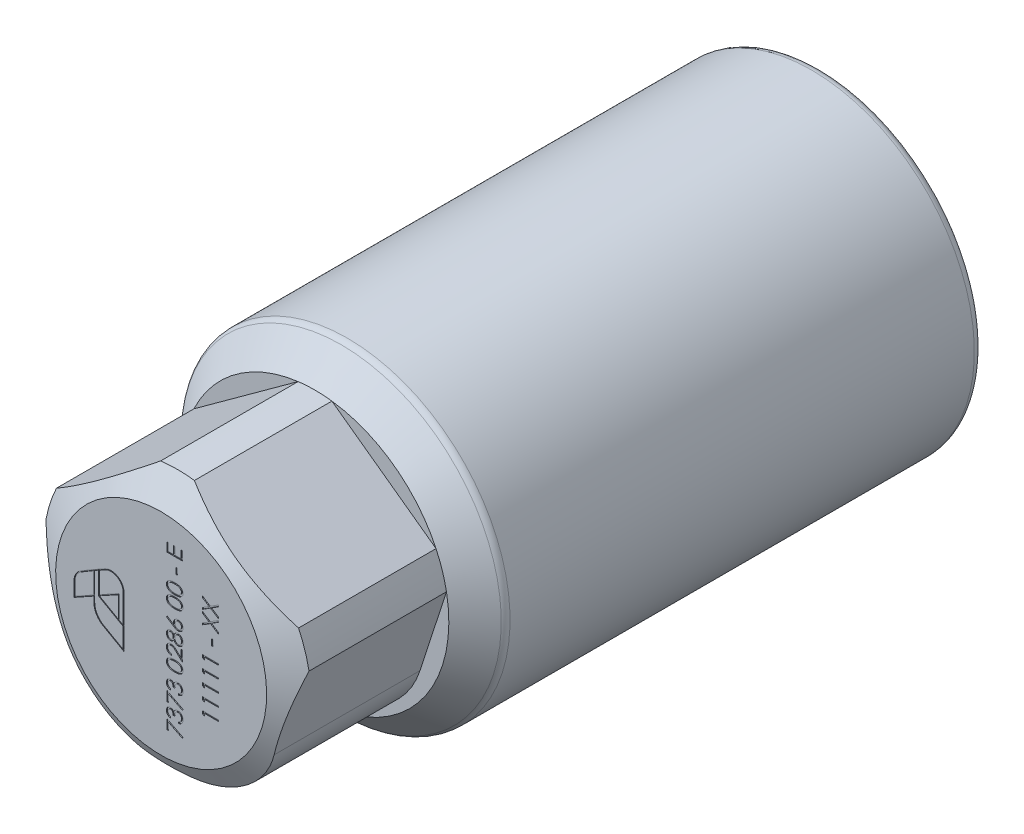
SolidWorks part; units mm, degrees
material "4340 H/T-Y"
ref_plane "Front Plane" through (0, 0, 0) normal (0, 0, 1) x (1, 0, 0)
ref_plane "Top Plane" through (0, 0, 0) normal (0, 1, 0) x (1, 0, 0)
ref_plane "Right Plane" through (0, 0, 0) normal (1, 0, 0) x (0, 0, -1)
sketch "Sketch1" plane through (0, 0, 0) normal (1, 0, 0) x (0, 0, -1)
  line L0 (0, 10.75) -> (0, 17.5)
  line L3 (-1, 18.5) -> (-53.8108, 18.5)
  line L4 (-54.5179, 18.2071) -> (-57.5, 15.225)
  line L5 (-57.5, 15.225) -> (-73.138, 15.225)
  line L6 (-0.5, 10.25) -> (-5, 10.25)
  line L7 (-5, 10.25) -> (-6.25, 9)
  line L8 (-6.25, 9) -> (-49.2721, 9)
  line L9 (-49.2721, 9) -> (-53, 0)
  line L10 (-53, 0) -> (-75, 0)
  line L11 (0, 0) -> (-53, 0) construction
  line L13 (-0.5, 10.25) -> (0, 10.75)
  line L14 (-73.138, 15.225) -> (-75, 12)
  line L15 (-75, 12) -> (-75, 0)
  arc A0 (-1, 18.5) -> (0, 17.5) centre (-1, 17.5) cw
  arc A1 (-54.5179, 18.2071) -> (-53.8108, 18.5) centre (-53.8108, 17.5) cw
  point P0 (0, 10.25)
  point P1 (0, 15.75)
  point P22 (-54.225, 18.5)
  dimension "D14" = 30.45
  dimension "D19" = 1
  dimension "D4" = 1
  dimension "D2" = 20.5
  dimension "D3" = 37
  dimension "D6" = 45
  dimension "D7" = 17.5
  dimension "D8" = 30
  dimension "D9" = 67.5
  dimension "D10" = 53
  dimension "D11" = 18
  dimension "D12" = 45
  dimension "D13" = 5
  dimension "D18" = 75
  dimension "D20" = 24
revolve "Revolve1" add sketch "Sketch1" angle 360 about L11
cosmetic thread "Cosmetic Thread1" parameters "D1"=40, "D2"=20
sketch "Sketch2" plane through (0, 0, 75) normal (0, 0, 1) x (1, 0, 0)
  line L0 (0, 0) -> (29.3551, 0) construction
  line L1 (0, 0) -> (0, 21.4203) construction
  line L2 (0, 16.5) -> (-15.6924, 5.0988)
  line L3 (0, 16.5) -> (15.6924, 5.0988)
  line L4 (-15.6924, 5.0988) -> (-11.9436, -6.439)
  line L5 (-2.433, -13.3488) -> (2.433, -13.3488)
  line L6 (11.9436, -6.439) -> (15.6924, 5.0988)
  circle A0 centre (0, 0) radius 16.5 construction
  arc A1 (11.9436, -6.439) -> (2.433, -13.3488) centre (2.433, -3.3488) cw
  arc A2 (-11.9436, -6.439) -> (-2.433, -13.3488) centre (-2.433, -3.3488) ccw
  point P11 (9.6985, -13.3488)
  point P14 (-9.6985, -13.3488)
  dimension "D3" = 33
  dimension "D4" = 10
  dimension "D1" = 108
  dimension "D2" = 108
sketch "Sketch3" plane through (0, 19, 75) normal (0, 0, -1) x (1, 0, 0)
  line L0 (2.4507, 8.0901) -> (2.4507, 29.7889) construction
  text T0 "7373 0286 00 - E\r\n11111 - XX" font "Century Gothic" height 1.8
  point P5 (2.4507, -21.4712)
  point P6 (2.4507, 18.9395)
  line B0 (-4.2098, 17.1363) -> (-4.2098, 20.4047)
  line B1 (-4.8761, 17.6204) -> (-4.8761, 20.0259)
  line B2 (-4.3098, 20.3479) -> (-4.7761, 20.0827)
  line B3 (-7.6541, 19.1467) -> (-7.6541, 19.7168)
  line B4 (-9.918, 20.4047) -> (-7.6541, 19.1467)
  line B5 (-4.8761, 17.6204) -> (-7.0234, 18.8049)
  line B6 (-7.0234, 16.1754) -> (-6.507, 15.8767)
  line B7 (-9.918, 18.8007) -> (-9.918, 20.4047)
  line B8 (-7.6541, 16.5194) -> (-7.0234, 16.1754)
  line B9 (-7.6541, 16.5194) -> (-9.1106, 17.3832)
  line B10 (-4.2098, 20.4047) -> (-4.2098, 22.9022)
  line B11 (-6.679, 21.4981) -> (-4.2098, 22.9022)
  line B12 (-7.1237, 16.3211) -> (-7.5541, 16.5764)
  line B13 (-9.818, 18.8007) -> (-9.818, 20.2348)
  line B14 (-9.818, 20.2348) -> (-7.6541, 19.0323)
  line B15 (-7.5541, 19.7168) -> (-7.5541, 16.5764)
  line B16 (-6.6273, 21.4125) -> (-4.3098, 22.7303)
  line B17 (-4.3098, 20.4629) -> (-4.3098, 22.7303)
  line B18 (-4.2098, 18.7705) -> (-11.8954, 18.7705) construction
  line B19 (-7.1237, 18.8628) -> (-7.1237, 16.3211)
  line B20 (-4.3098, 20.4629) -> (-7.1237, 18.8628)
  line B21 (-7.0234, 16.291) -> (-6.455, 15.9621)
  line B22 (-4.3098, 17.1363) -> (-4.3098, 20.3479)
  line B23 (-7.6541, 19.0323) -> (-7.6541, 16.6357)
  line B24 (-7.6541, 16.6357) -> (-9.0596, 17.4692)
  line B25 (-4.7761, 17.451) -> (-4.7761, 20.0827)
  line B26 (-4.7761, 17.451) -> (-7.0234, 18.6906)
  line B27 (-7.0234, 18.6906) -> (-7.0234, 16.291)
  line B28 (-4.8761, 20.0259) -> (-7.0234, 18.8049)
  arc B29 (-9.1106, 17.3832) -> (-9.918, 18.8007) centre (-8.27, 18.8007) cw
  arc B30 (-4.2098, 17.1363) -> (-6.507, 15.8767) centre (-5.7038, 17.1363) cw
  arc B31 (-7.6541, 19.7168) -> (-6.679, 21.4981) centre (-5.5394, 19.7168) cw
  arc B32 (-9.0596, 17.4692) -> (-9.818, 18.8007) centre (-8.27, 18.8007) cw
  arc B33 (-7.5541, 19.7168) -> (-6.6273, 21.4125) centre (-5.5394, 19.7168) cw
  arc B34 (-4.3098, 17.1363) -> (-6.455, 15.9621) centre (-5.7038, 17.1363) cw
sketch_block_instance "SKETCH LOGO-4"
sketch_block "SKETCH LOGO" parameters "D1"=29.059, "D2"=11.4163, "D3"=29.624, "D4"=6.8884
ref_plane "Plane1" through (0, 0, 57.5) normal (0, 0, -1) x (-1, 0, 0)
extrude "Cut-Extrude3" cut sketch "Sketch2" against normal up to surface (17.5 mm away) flip side to cut up to plane "Plane1"
extrude "P/N Cut-Extrude7" cut sketch "Sketch3" along normal blind 0.1
